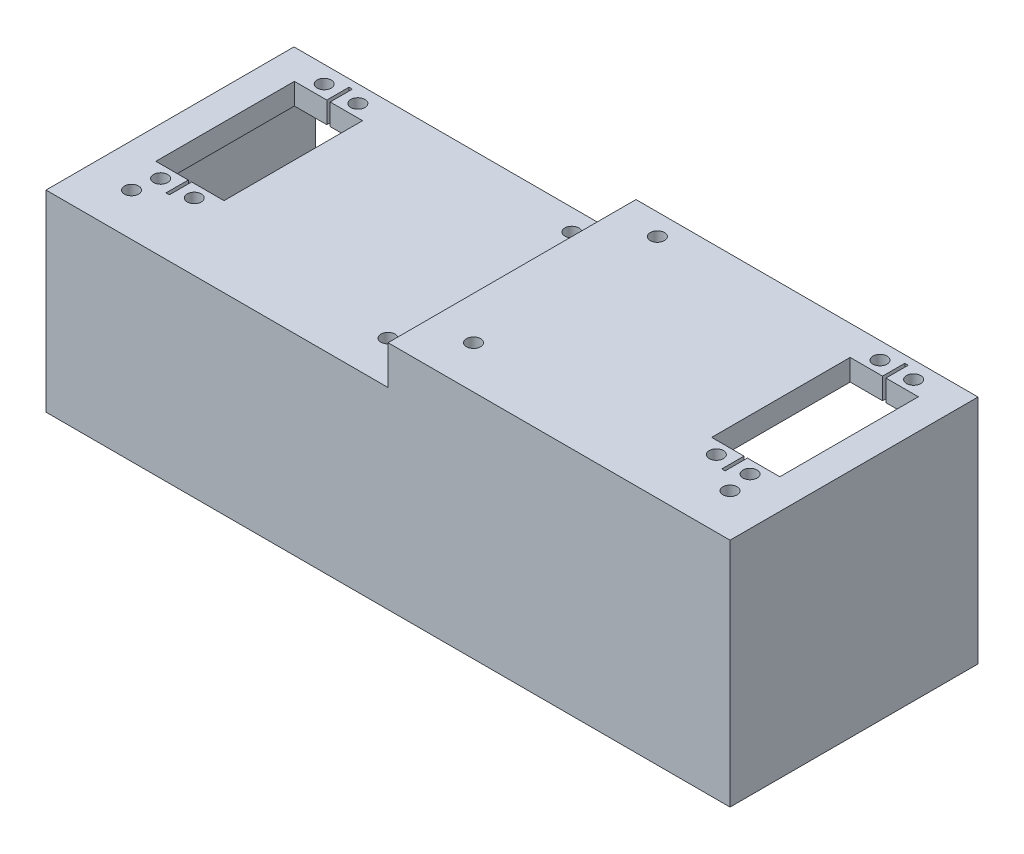
SolidWorks part; units mm, degrees
ref_plane "Front Plane" through (0, 0, 0) normal (0, 0, 1) x (1, 0, 0)
ref_plane "Top Plane" through (0, 0, 0) normal (0, 1, 0) x (1, 0, 0)
ref_plane "Right Plane" through (0, 0, 0) normal (1, 0, 0) x (0, 0, -1)
sketch "Sketch1" plane through (0, 0, 0) normal (0, 0, 1) x (1, 0, 0)
  line L1 (0, 0) -> (203.2, 0)
  line L2 (0, 0) -> (0, 57.15)
  line L3 (0, 57.15) -> (203.2, 57.15)
  line L4 (203.2, 0) -> (203.2, 57.15)
  line L5 (101.6, 57.15) -> (203.2, 57.15)
  line L6 (101.6, 57.15) -> (101.6, 68.675)
  line L7 (101.6, 68.675) -> (203.2, 68.675)
  line L8 (203.2, 57.15) -> (203.2, 68.675)
  dimension "D1" = 203.2
  dimension "D2" = 57.15
  dimension "D3" = 11.525
extrude "Boss-Extrude1" add sketch "Sketch1" along normal mid plane 73.66 contours L1 L4 L3 L2 | L3 L8 L7 L6 region at (101.6, 28.575, 0) region at (152.4, 62.9125, 0)
sketch "Sketch4" plane through (0, 0, -36.83) normal (0, 0, -1) x (-1, 0, 0)
  line L6 (-107.95, 50.8) -> (-107.95, 6.35)
  line L7 (-95.25, 50.8) -> (-95.25, 6.35)
  line L8 (-101.6, 57.15) -> (-101.6, 68.675) construction
  line L9 (-95.25, 6.35) -> (-6.35, 6.35)
  line L12 (-196.85, 6.35) -> (-6.35, 6.35)
  line L13 (-6.35, 6.35) -> (-6.35, 50.8)
  line L14 (-6.35, 50.8) -> (-107.95, 50.8)
  line L15 (-107.95, 50.8) -> (-107.95, 62.325)
  line L16 (-107.95, 62.325) -> (-196.85, 62.325)
  line L17 (-196.85, 62.325) -> (-196.85, 6.35)
  line L18 (-196.85, 6.35) -> (-107.95, 6.35)
  line L19 (-6.35, 6.35) -> (-6.35, 50.8)
  line L20 (-6.35, 50.8) -> (-95.25, 50.8)
  line L21 (-107.95, 50.8) -> (-107.95, 62.325)
  line L22 (-107.95, 62.325) -> (-196.85, 62.325)
  line L23 (-196.85, 62.325) -> (-196.85, 6.35)
  dimension "D2" = 6.35
  dimension "D1" = 6.35
extrude "Cut-Extrude2" cut sketch "Sketch4" against normal offset from surface (67.31 mm away) 6.35 up to face at (101.6, 41.9417, 36.83)
sketch "Sketch2" plane through (0, 57.15, 0) normal (0, 1, 0) x (1, 0, 0)
  line L0 (8.923, 28.034) -> (29.177, -13.12) construction
  line L5 (8.923, 28.034) -> (18.55, 28.034)
  line L6 (8.923, 28.034) -> (8.923, -13.12)
  line L7 (8.923, -13.12) -> (18.55, -13.12)
  line L12 (29.177, 28.034) -> (29.177, -13.12)
  line L17 (29.177, 28.034) -> (8.923, -13.12) construction
  line L18 (14.05, 31.757) -> (24.05, -16.843) construction
  line L19 (14.05, -16.843) -> (24.05, 31.757) construction
  line L20 (19.55, -13.12) -> (29.177, -13.12)
  line L21 (19.55, -13.12) -> (19.55, -19.724)
  line L22 (19.55, -19.724) -> (18.55, -19.724)
  line L23 (18.55, -13.12) -> (18.55, -19.724)
  line L24 (19.05, 7.457) -> (-13.3966, 7.457) construction
  line L25 (19.55, 34.638) -> (18.55, 34.638)
  line L26 (19.55, 28.034) -> (19.55, 34.638)
  line L27 (18.55, 28.034) -> (18.55, 34.638)
  line L28 (19.55, 28.034) -> (29.177, 28.034)
  line L29 (0, 36.83) -> (101.6, 36.83) construction
  line L30 (0, -36.83) -> (0, 36.83) construction
  line L31 (101.6, -36.83) -> (101.6, 36.83) construction
  line L32 (184.15, 7.457) -> (216.5966, 7.457) construction
  line L33 (189.15, -16.843) -> (179.15, 31.757) construction
  line L34 (189.15, 31.757) -> (179.15, -16.843) construction
  line L35 (174.023, 28.034) -> (194.277, -13.12) construction
  line L36 (194.277, 28.034) -> (174.023, -13.12) construction
  line L37 (183.65, 28.034) -> (174.023, 28.034)
  line L38 (184.65, 28.034) -> (184.65, 34.638)
  line L39 (183.65, 28.034) -> (183.65, 34.638)
  line L40 (183.65, 34.638) -> (184.65, 34.638)
  line L41 (184.65, -13.12) -> (184.65, -19.724)
  line L42 (183.65, -19.724) -> (184.65, -19.724)
  line L43 (183.65, -13.12) -> (183.65, -19.724)
  line L44 (183.65, -13.12) -> (174.023, -13.12)
  line L45 (174.023, 28.034) -> (174.023, -13.12)
  line L46 (194.277, -13.12) -> (184.65, -13.12)
  line L47 (194.277, 28.034) -> (194.277, -13.12)
  line L48 (194.277, 28.034) -> (184.65, 28.034)
  circle A4 centre (14.05, -16.843) radius 2.1
  circle A5 centre (24.05, -16.843) radius 2.1
  circle A6 centre (14.05, 31.757) radius 2.1
  circle A7 centre (24.05, 31.757) radius 2.1
  circle A8 centre (179.15, 31.757) radius 2.1
  circle A9 centre (189.15, 31.757) radius 2.1
  circle A10 centre (179.15, -16.843) radius 2.1
  circle A11 centre (189.15, -16.843) radius 2.1
  point P8 (19.05, -19.724)
  point P17 (19.05, 7.457)
  point P18 (19.05, 7.457)
  point P27 (19.05, 17.78)
  point P58 (184.15, 17.78)
  dimension "D3" = 4.2
  dimension "D1" = 10
  dimension "D2" = 48.6
  dimension "D4" = 41.154
  dimension "D5" = 20.254
  dimension "D6" = 1
  dimension "D7" = 6.604
  dimension "D8" = 30.9
  dimension "D9" = 19.05
  dimension "D10" = 19.05
extrude "Cut-Extrude3" cut sketch "Sketch2" along normal through all from surface starting at face at (50.8, 50.8, -3.175)
sketch "Sketch6" plane through (0, 6.35, 0) normal (0, 1, 0) x (1, 0, 0)
  line L0 (6.35, -30.48) -> (6.35, 36.83) construction
  line L1 (95.25, -30.48) -> (6.35, -30.48) construction
  line L3 (95.25, -30.48) -> (95.25, 36.83) construction
  line L5 (95.25, 36.83) -> (6.35, 36.83) construction
  line L6 (101.6, -36.83) -> (101.6, 36.83) construction
  circle A0 centre (19.05, 24.13) radius 2.1
  circle A1 centre (88.9, 30.48) radius 2.1
  circle A2 centre (88.9, -24.13) radius 2.1
  circle A3 centre (12.7, -24.13) radius 2.1
  circle A4 centre (190.5, -24.13) radius 2.1
  circle A5 centre (114.3, -24.13) radius 2.1
  circle A6 centre (114.3, 30.48) radius 2.1
  circle A7 centre (184.15, 24.13) radius 2.1
  dimension "D1" = 4.2
  dimension "D2" = 6.35
  dimension "D3" = 6.35
  dimension "D4" = 6.35
  dimension "D5" = 6.35
  dimension "D6" = 12.7
  dimension "D7" = 12.7
extrude "Cut-Extrude4" cut sketch "Sketch6" against normal through all both and the other way through all
equation "\"D3@Sketch1\"= 0.875 - 10.7mm"
equation "\"D3@Sketch2\"=4.2mm"
equation "\"D1@Sketch6\"=4.2mm"
